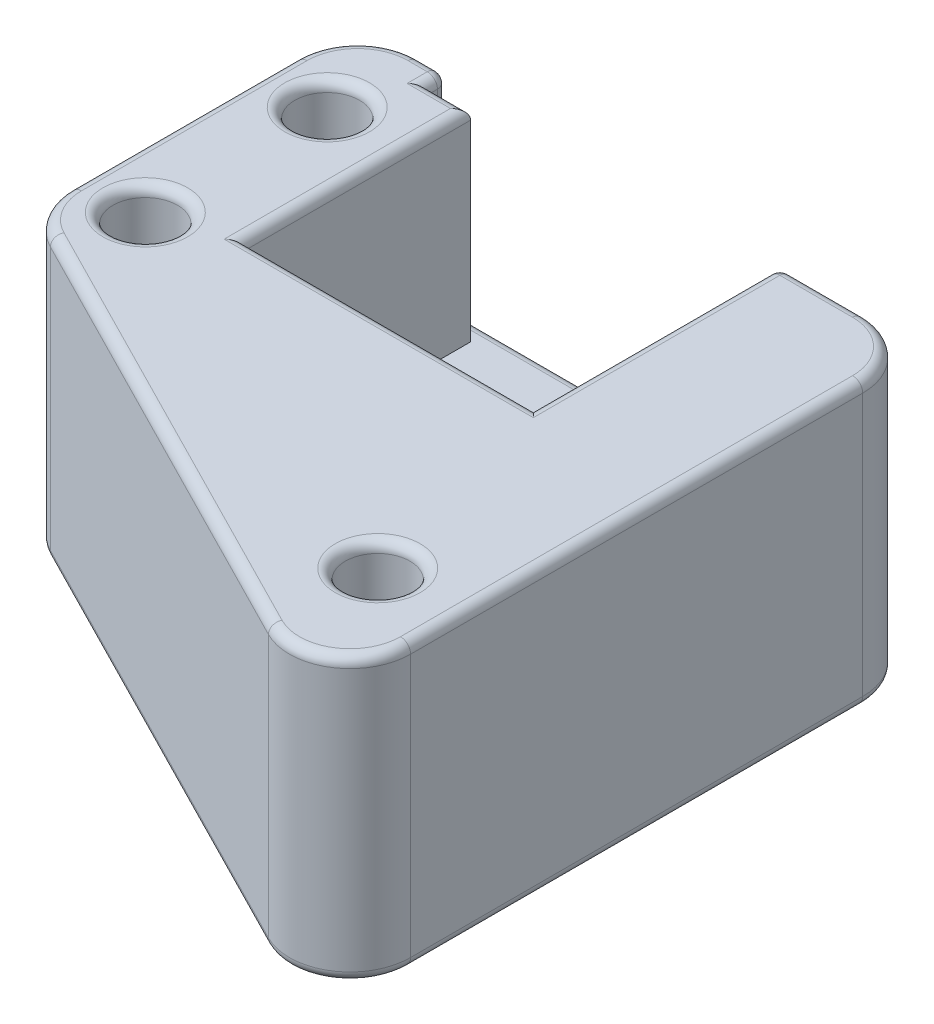
SolidWorks part; units mm, degrees
ref_plane "Front Plane" through (0, 0, 0) normal (0, 0, 1) x (1, 0, 0)
ref_plane "Top Plane" through (0, 0, 0) normal (0, 1, 0) x (1, 0, 0)
ref_plane "Right Plane" through (0, 0, 0) normal (1, 0, 0) x (0, 0, -1)
sketch "Sketch1" plane through (0, 0, 0) normal (0, 1, 0) x (1, 0, 0)
  line L0 (-3.25, 0) -> (3.25, 0) construction
  line L1 (6.4, 5) -> (-6.4, 5) construction
  line L2 (-14, -10) -> (14, -10)
  line L3 (-14, -10) -> (-14, 6)
  line L4 (-14, 6) -> (14, 6)
  line L5 (14, -10) -> (14, 6)
  line L6 (-11, -7.5) -> (10, -7.5) construction
  line L7 (0, 0) -> (0, -10) construction
  line L8 (-11, -7.5) -> (-11, 1.5) construction
  line L9 (-11, 1.5) -> (10, 1.5) construction
  line L10 (10, 1.5) -> (10, -7.5) construction
  circle A0 centre (3.25, 0) radius 0.85
  circle A1 centre (-3.25, 0) radius 0.85
  circle A2 centre (-11, -7.5) radius 1.6
  circle A3 centre (10, -7.5) radius 1.6 construction
  circle A4 centre (-11, -7.5) radius 3 construction
  circle A5 centre (-11, 1.5) radius 1.6
  circle A6 centre (10, 1.5) radius 1.6 construction
  circle A7 centre (-11, 1.5) radius 3 construction
  point P4 (0, 0)
  dimension "D1" = 1.7
  dimension "D2" = 6.5
  dimension "D6" = 3.2
  dimension "D8" = 6
  dimension "D9" = 9
  dimension "D10" = 2.5
  dimension "D3" = 16
  dimension "D4" = 28
  dimension "D5" = 1
  dimension "D7" = 21
  dimension "D11" = 4
extrude "Boss-Extrude1" add sketch "Sketch1" along normal blind 4
sketch "Sketch2" plane through (0, 4, 0) normal (0, 1, 0) x (1, 0, 0)
  line L0 (-9.5462, 6) -> (-9.5462, 5)
  line L1 (-7.4, -6.2) -> (6.9, -6.2)
  line L2 (6.9, -6.2) -> (6.9, 6)
  line L3 (-9.5462, 6) -> (-14, 6)
  line L4 (-14, 6) -> (-14, -10)
  line L5 (-14, -10) -> (14, -10)
  line L6 (14, -10) -> (14, 6)
  line L7 (14, 6) -> (6.9, 6)
  line L8 (14, -10) -> (14, 6) construction
  line L9 (14, 6) -> (-14, 6) construction
  line L10 (6.4, 1.3) -> (6.4, 5) construction
  line L11 (-14, 6) -> (-14, -10) construction
  line L13 (4.75, -1.2) -> (6.4, -1.2) construction
  line L14 (-9.5462, 5) -> (-7.4, 5)
  line L15 (-7.4, 5) -> (-7.4, -6.2)
  line L16 (-6.4, 5) -> (6.4, 5) construction
  line L17 (-6.4, 5) -> (-6.4, 1.3) construction
  circle A0 centre (-11, -7.5) radius 1.6 construction
  circle A1 centre (-11, -7.5) radius 1.6
  circle A5 centre (-11, 1.5) radius 1.6 construction
  circle A7 centre (-11, 1.5) radius 1.6
  dimension "D1" = 0.5
  dimension "D2" = 5
  dimension "D3" = 2
  dimension "D4" = 1
extrude "Boss-Extrude2" add sketch "Sketch2" along normal blind 10
sketch "Sketch4" plane through (0, 0, 0) normal (0, -1, 0) x (1, 0, 0)
  line L0 (14, 10) -> (14, 24.2667)
  line L1 (14, 24.2667) -> (-14, 10)
  line L2 (10, 17) -> (10, 7.5) construction
  line L3 (14, 10) -> (-14, 10)
  line L4 (-11, 7.5) -> (10, 7.5) construction
  circle A0 centre (10, 17) radius 1.6
  circle A2 centre (-11, 7.5) radius 1.6 construction
  point P9 (0, 0)
  dimension "D1" = 9.5
  dimension "D3" = 3.2
  dimension "D2" = 27
  dimension "D4" = 21
extrude "Boss-Extrude3" add sketch "Sketch4" against normal through all
fillet "Fillet2" radius 3 4 edges at (-14, 7, -6) (14, 7, -6) (-14, 7, 10) (14, 7, 24.2667)
fillet "Fillet1" radius 0.5 33 edges at (-3.25, 0, 0.85) (-14, 0, 2.5808) (14, 0, 8.1856) (3.25, 0, 0.85) (-11, 0, 9.1) (6.9, 9, -6) (-1.3231, 4, -6) (-9.5462, 9, -6) (0, 0, -6) (-9.5462, 14, -5.5) (-8.4731, 14, -5) (-7.4, 14, 0.6) (-0.25, 14, 6.2) (6.9, 14, 0.1) (8.95, 14, -6) (14, 14, 8.1856) (-14, 14, 2.5808) (-10.2731, 14, -6) (-11, 14, 9.1) (-11, 0, 0.1) (-11, 14, 0.1) (10, 0, 15.4) (-1.362, 0, 16.4394) (10, 14, 15.4) (-1.362, 14, 16.4394) (-13.5579, 0, 9.7291) (12.5675, 0, 21.9291) (13.1213, 0, -5.1213) (-13.1213, 0, -5.1213) (13.1213, 14, -5.1213) (12.5675, 14, 21.9291) (-13.5579, 14, 9.7291) (-13.1213, 14, -5.1213)
